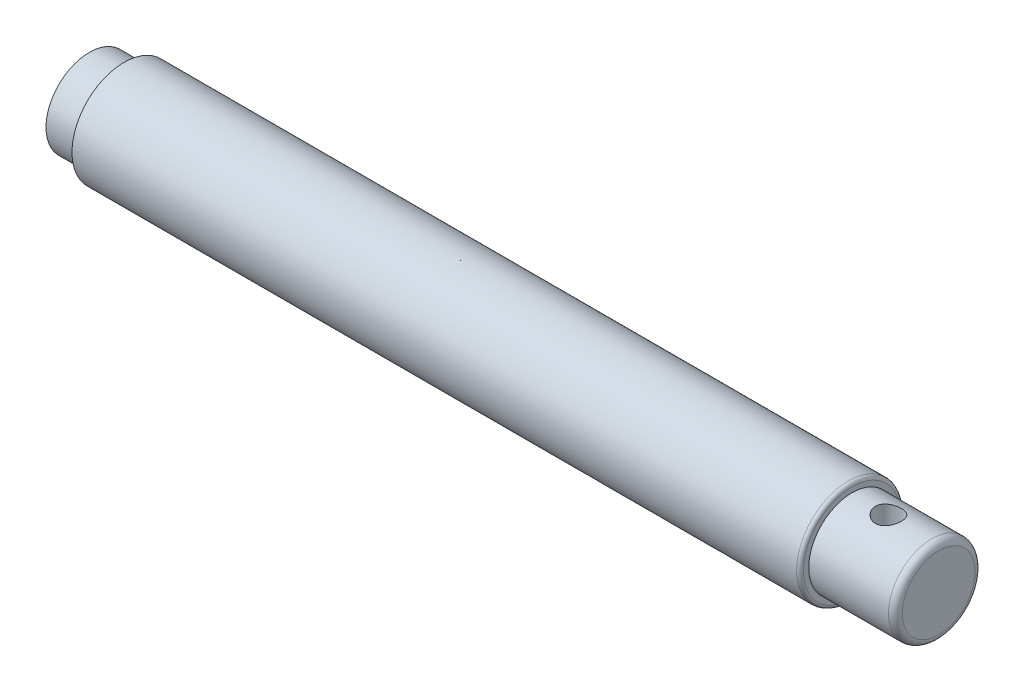
SolidWorks part; units mm, degrees
ref_plane "Plano frontal" through (0, 0, 0) normal (0, 0, 1) x (1, 0, 0)
ref_plane "Plano superior" through (0, 0, 0) normal (0, 1, 0) x (1, 0, 0)
ref_plane "Plano direito" through (0, 0, 0) normal (1, 0, 0) x (0, 0, -1)
sketch "Esboço1" plane through (0, 0, 0) normal (1, 0, 0) x (0, 0, -1)
  circle A0 centre (0, 0) radius 15
  circle A1 centre (0, 0) radius 10
  dimension "D1" = 30
  dimension "D2" = 20
extrude "Ressalto-extrusão1" add sketch "Esboço1" along normal blind 210 contours A1 | A0
sketch "Esboço2" plane through (0, 0, 0) normal (-1, 0, 0) x (0, 0, 1)
  line L0 (0, 15) -> (0, 0) construction
  circle A0 centre (0, 0) radius 15 construction
  circle A1 centre (0, 0) radius 10
  circle A3 centre (0, 0) radius 12.5
  dimension "D1" = 20
extrude "Ressalto-extrusão3" add sketch "Esboço2" against normal blind 15 from offset 10
sketch "Esboço4" plane through (0, 0, 0) normal (0, 1, 0) x (1, 0, 0)
  point P4 (0, 0)
sketch3d "3DSketch1"
  point P0 (150.2064, 3.6276, 9.3188)
sketch "Esboço6" plane through (210, 0, 0) normal (1, 0, 0) x (0, 0, -1)
  circle A0 centre (0, 0) radius 12.5
extrude "Ressalto-extrusão4" add sketch "Esboço6" along normal blind 25 separate body
fillet "Filete2" radius 2 1 edges at (235, 0, -12.5)
sketch "Esboço7" plane through (0, 0, 0) normal (0, 1, 0) x (1, 0, 0)
  line L0 (233, 12.5) -> (233, -12.5) construction
  circle A0 centre (220.5, 0) radius 3.75
  dimension "D1" = 7.5
  dimension "D2" = 12.5
extrude "Corte-extrusão4" cut sketch "Esboço7" against normal blind 20 and the other way blind 20
fillet "Filete3" radius 1 1 edges at (210, 0, -15)
ref_plane "Plano1" through (0, 0, 15) normal (0, 0, 1) x (1, 0, 0)
sketch "Esboço9" plane through (0, 0, 15) normal (0, 0, 1) x (1, 0, 0)
  line L0 (0, -15) -> (209, -15) construction
  line L1 (233, -12.5) -> (233, 12.5) construction
  circle A3 centre (146, -21) radius 10
  circle A4 centre (165, -21) radius 10
  circle A5 centre (184, -21) radius 10
  dimension "D1" = 6
  dimension "D2" = 20
  dimension "D3" = 49
  dimension "D4" = 19
  dimension "D5" = 19
extrude "Corte-extrusão6" cut sketch "Esboço9" against normal blind 30 contours A5 | A4 | A3
ref_plane "Plano2" through (0, -15, 0) normal (0, 1, 0) x (1, 0, 0)
fillet "Filete5" radius 3 3 edges at (138.0151, -14.98, 0.775) (176.0151, -14.98, 0.775) (157.0151, -14.98, 0.775)
